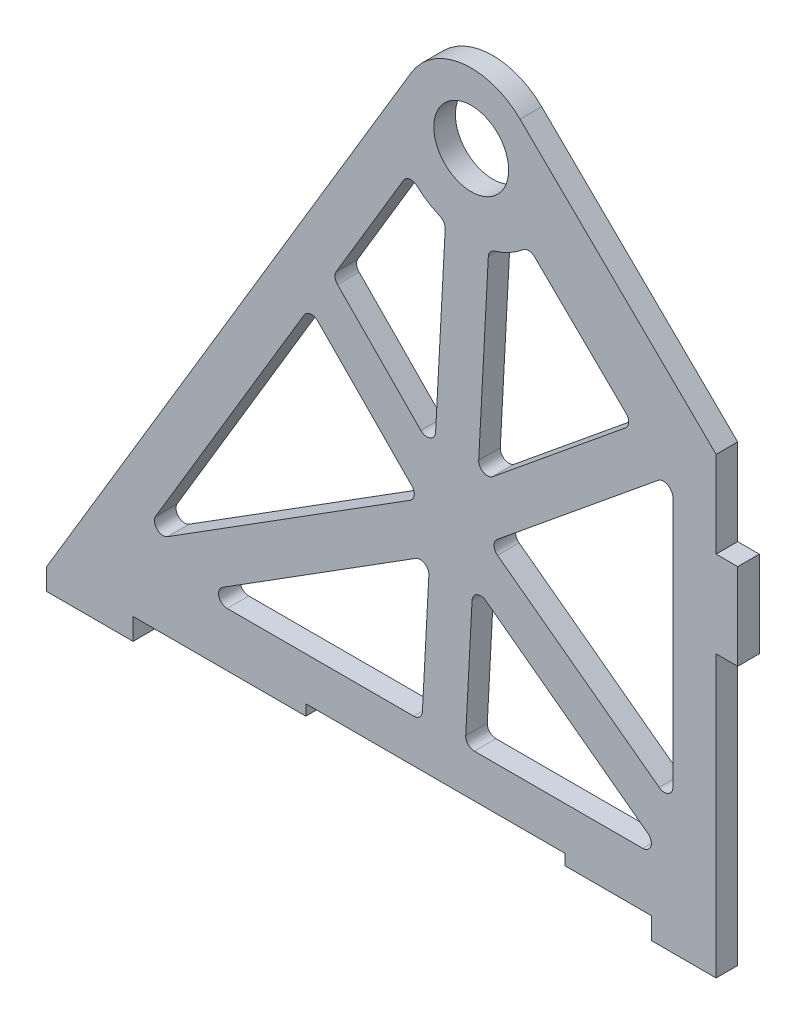
SolidWorks part; units mm, degrees
ref_plane "Front Plane" through (0, 0, 0) normal (0, 0, 1) x (1, 0, 0)
ref_plane "Top Plane" through (0, 0, 0) normal (0, 1, 0) x (1, 0, 0)
ref_plane "Right Plane" through (0, 0, 0) normal (1, 0, 0) x (0, 0, -1)
sketch "Sketch2" plane through (0, 0, 0) normal (0, 0, 1) x (1, 0, 0)
  line L0 (1566.672, 2.5421) -> (1649.222, 2.5421) construction
  line L1 (1592.072, 2.5421) -> (1642.872, 2.5421)
  line L2 (1566.672, 2.5421) -> (1673.8864, 181.9515)
  line L4 (1642.872, 2.5421) -> (1642.872, 5.7171)
  line L6 (1566.672, 2.5421) -> (1566.672, -3.8079)
  line L7 (1566.672, -3.8079) -> (1592.072, -3.8079)
  line L8 (1592.072, 2.5421) -> (1592.072, -3.8079)
  line L13 (1642.872, 5.7171) -> (1719.072, 5.7171)
  line L14 (1719.072, 5.7171) -> (1719.072, 2.5421)
  line L16 (1719.072, 2.5421) -> (1744.472, 2.5421)
  line L17 (1566.672, -33.6061) -> (1769.872, -33.6061) construction
  line L18 (1744.472, 2.5421) -> (1744.472, -3.8079)
  line L19 (1744.472, -3.8079) -> (1763.522, -3.8079)
  line L20 (1763.522, -3.8079) -> (1763.522, 78.7421)
  line L22 (1763.522, 129.5421) -> (1705.8766, 186.0765)
  line L23 (1763.522, 104.1421) -> (1763.522, 129.5421)
  line L24 (1763.522, 104.1421) -> (1769.872, 104.1421)
  line L26 (1763.522, 78.7421) -> (1769.872, 78.7421)
  line L27 (1769.872, 104.1421) -> (1769.872, 78.7421)
  arc A0 (1705.8766, 186.0765) -> (1673.8864, 181.9515) centre (1691.5051, 171.4226) ccw
  circle A1 centre (1691.5051, 171.4226) radius 11 construction
  circle A2 centre (1691.5051, 171.4226) radius 4 construction
  circle A3 centre (1691.5051, 171.4226) radius 11
  dimension "D3" = 22
  dimension "D4" = 9.525
  dimension "D5" = 8
  dimension "D6" = 22
  dimension "D1" = 168.8805
  dimension "D2" = 124.8331
  dimension "D7" = 6.35
  dimension "D8" = 25.4
  dimension "D9" = 19.05
  dimension "D10" = 6.35
  dimension "D11" = 44.45
  dimension "D12" = 203.2
  dimension "D13" = 76.2
  dimension "D14" = 3.175
  dimension "D15" = 133.35
  dimension "D16" = 6.35
  dimension "D17" = 25.4
  dimension "D18" = 25.4
extrude "Boss-Extrude1" add sketch "Sketch2" along normal blind 6.35
sketch "Sketch4" plane through (0, 0, 6.35) normal (0, 0, 1) x (1, 0, 0)
  line L0 (1673.3123, 156.2334) -> (1577.5737, -3.9728)
  line L1 (1691.5051, 171.4226) -> (1750.822, 113.2489)
  line L2 (1684.7881, 175.4367) -> (1577.5737, -3.9728) construction
  line L3 (1590.9538, 18.4171) -> (1750.822, 18.4171)
  line L4 (1686.3016, 73.3904) -> (1617.2071, 143.6449) construction
  line L7 (1681.7742, 68.9378) -> (1612.6797, 139.1923)
  line L10 (1690.8289, 77.843) -> (1621.7344, 148.0975)
  line L13 (1566.672, 2.5421) -> (1566.672, -3.8079)
  line L14 (1566.672, -3.8079) -> (1592.072, -3.8079)
  line L15 (1592.072, -3.8079) -> (1592.072, 2.5421)
  line L16 (1592.072, 2.5421) -> (1642.872, 2.5421)
  line L17 (1642.872, 2.5421) -> (1642.872, 5.7171)
  line L18 (1642.872, 5.7171) -> (1719.072, 5.7171)
  line L19 (1719.072, 5.7171) -> (1719.072, 2.5421)
  line L20 (1719.072, 2.5421) -> (1744.472, 2.5421)
  line L21 (1744.472, -3.8079) -> (1763.522, -3.8079)
  line L22 (1744.472, 2.5421) -> (1744.472, -3.8079)
  line L23 (1719.072, 2.5421) -> (1744.472, 2.5421)
  line L24 (1763.522, -3.8079) -> (1763.522, 78.7421)
  line L25 (1673.8864, 181.9515) -> (1566.672, 2.5421)
  line L26 (1566.672, 2.5421) -> (1566.672, -3.8079)
  line L27 (1566.672, -3.8079) -> (1592.072, -3.8079)
  line L28 (1592.072, -3.8079) -> (1592.072, 2.5421)
  line L29 (1592.072, 2.5421) -> (1642.872, 2.5421)
  line L30 (1642.872, 2.5421) -> (1642.872, 5.7171)
  line L31 (1642.872, 5.7171) -> (1719.072, 5.7171)
  line L32 (1719.072, 5.7171) -> (1719.072, 2.5421)
  line L34 (1744.472, -3.8079) -> (1763.522, -3.8079)
  line L35 (1744.472, 2.5421) -> (1744.472, -3.8079)
  line L38 (1673.8864, 181.9515) -> (1566.672, 2.5421)
  line L39 (1686.3016, 73.3904) -> (1776.688, 147.3217) construction
  line L42 (1682.2812, 78.3056) -> (1772.6676, 152.2368)
  line L45 (1690.3219, 68.4752) -> (1780.7084, 142.4065)
  line L46 (1686.3016, 73.3904) -> (1535.3984, -21.6576) construction
  line L47 (1750.822, 113.2489) -> (1750.822, 18.4171)
  line L48 (1689.6858, 68.0174) -> (1538.7827, -27.0307)
  line L49 (1682.9173, 78.7634) -> (1532.0142, -16.2846)
  line L50 (1686.3016, 73.3904) -> (1767.8024, 12.8123) construction
  line L51 (1690.0896, 78.4868) -> (1771.5905, 17.9087)
  line L52 (1682.5135, 68.294) -> (1764.0144, 7.7159)
  line L53 (1691.5051, 171.4226) -> (1681.8948, -9.6316) construction
  line L54 (1697.8462, 171.086) -> (1688.2358, -9.9682)
  line L55 (1685.1641, 171.7592) -> (1675.5537, -9.2951)
  line L60 (1763.522, -3.8079) -> (1763.522, 78.7421)
  line L61 (1763.522, 129.5421) -> (1705.8766, 186.0765)
  line L62 (1763.522, 129.5421) -> (1705.8766, 186.0765)
  line L68 (1763.522, 78.7421) -> (1769.872, 78.7421)
  line L69 (1763.522, 78.7421) -> (1769.872, 78.7421)
  line L70 (1769.872, 78.7421) -> (1769.872, 104.1421)
  line L71 (1769.872, 78.7421) -> (1769.872, 104.1421)
  line L72 (1769.872, 104.1421) -> (1763.522, 104.1421)
  line L73 (1769.872, 104.1421) -> (1763.522, 104.1421)
  line L74 (1763.522, 104.1421) -> (1763.522, 129.5421)
  line L75 (1763.522, 104.1421) -> (1763.522, 129.5421)
  arc A1 (1705.8766, 186.0765) -> (1673.8864, 181.9515) centre (1691.5051, 171.4226) ccw
  arc A2 (1705.8766, 186.0765) -> (1673.8864, 181.9515) centre (1691.5051, 171.4226) ccw
  circle A4 centre (1691.5051, 171.4226) radius 23.7
  circle A5 centre (1691.5051, 171.4226) radius 23.7
  arc A14 (1681.7742, 68.9378) -> (1690.8289, 77.843) centre (1686.3016, 73.3904) ccw
  arc A15 (1621.7344, 148.0975) -> (1612.6797, 139.1923) centre (1617.2071, 143.6449) ccw
  arc A16 (1682.2812, 78.3056) -> (1690.3219, 68.4752) centre (1686.3016, 73.3904) ccw
  arc A17 (1780.7084, 142.4065) -> (1772.6676, 152.2368) centre (1776.688, 147.3217) ccw
  arc A18 (1689.6858, 68.0174) -> (1682.9173, 78.7634) centre (1686.3016, 73.3904) ccw
  arc A19 (1532.0142, -16.2846) -> (1538.7827, -27.0307) centre (1535.3984, -21.6576) ccw
  arc A20 (1690.0896, 78.4868) -> (1682.5135, 68.294) centre (1686.3016, 73.3904) ccw
  arc A21 (1764.0144, 7.7159) -> (1771.5905, 17.9087) centre (1767.8024, 12.8123) ccw
  arc A22 (1697.8462, 171.086) -> (1685.1641, 171.7592) centre (1691.5051, 171.4226) ccw
  arc A23 (1675.5537, -9.2951) -> (1688.2358, -9.9682) centre (1681.8948, -9.6316) ccw
  point P15 (1651.7543, 108.5176)
  point P28 (1731.4948, 110.356)
  point P35 (1610.85, 25.8664)
  point P42 (1727.052, 43.1013)
  point P50 (1686.6999, 80.8955)
  point P55 (1681.4718, -9.6273)
  point P56 (1767.8024, 12.8123)
  point P57 (1535.3984, -21.6576)
  point P58 (1617.2071, 143.6449)
  point P59 (1776.688, 147.3217)
  point P60 (0, 0)
  point P61 (0, 0)
  point P62 (0, 0)
  dimension "D6" = 6.35
  dimension "D4" = 12.7
  dimension "D5" = 12.7
  dimension "D1" = 0
  dimension "D2" = 12.7
  dimension "D3" = 12.7
extrude "Cut-Extrude1" cut sketch "Sketch4" against normal through all contours L49 L7 L0 | A5 L0 L10 L55 | A5 L54 L42 L1 | L45 L51 L47 L1 | L52 L54 L3 | L55 L48 L3 region at (1671.2173, 123.5261, 6.35) region at (1637.86, 68.0487, 6.35) region at (1710.6147, 123.8805, 6.35) region at (1655.7577, 32.7722, 6.35) region at (1732.7096, 74.869, 6.35) region at (1710.4583, 32.6886, 6.35)
fillet "Fillet1" radius 2.54 21 edges at (1673.3123, 156.2334, 3.175) (1593.2749, 22.3011, 3.175) (1708.4258, 154.828, 3.175) (1750.822, 113.2489, 3.175) (1748.2022, 115.8182, 3.175) (1750.822, 33.3455, 3.175) (1696.624, 73.6299, 3.175) (1739.0804, 124.7643, 3.175) (1693.4043, 87.4037, 3.175) (1696.6359, 148.2846, 3.175) (1677.0247, 18.4171, 3.175) (1610.9378, 18.4171, 3.175) (1679.3106, 61.4824, 3.175) (1644.0607, 107.2845, 3.175) (1676.2444, 74.5604, 3.175) (1683.9538, 148.9578, 3.175) (1650.7933, 118.5507, 3.175) (1749.6172, 18.4171, 3.175) (1689.7425, 18.4171, 3.175) (1692.0151, 61.2316, 3.175) (1680.7243, 88.1172, 3.175)
